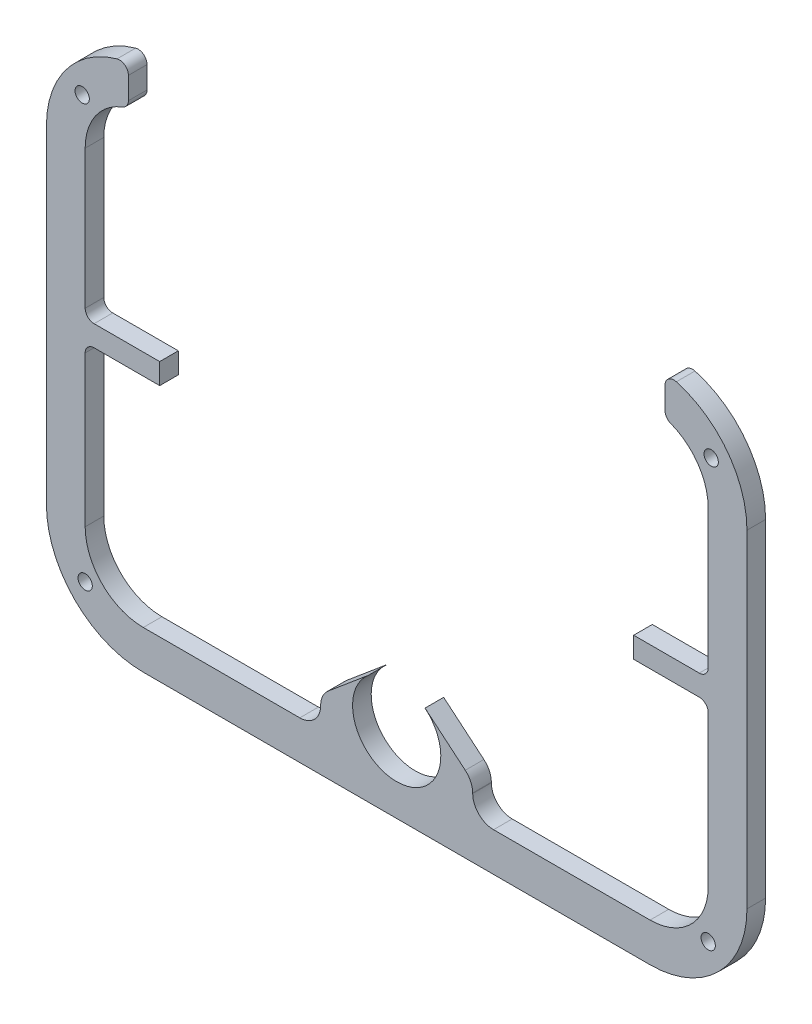
SolidWorks part; units mm, degrees
material "Delrin 2700 NC010, Low Viscosity Acetal Copolymer (SS)"
ref_plane "Front Plane" through (0, 0, 0) normal (0, 0, 1) x (1, 0, 0)
ref_plane "Top Plane" through (0, 0, 0) normal (0, 1, 0) x (1, 0, 0)
ref_plane "Right Plane" through (0, 0, 0) normal (1, 0, 0) x (0, 0, -1)
sketch "Sketch1" plane through (0, 0, 0) normal (0, 0, 1) x (1, 0, 0)
  line L0 (-21.59, -18.923) -> (-9.6321, -18.923)
  line L1 (21.59, 22.225) -> (-21.59, 22.225)
  line L2 (29.845, 13.97) -> (29.845, -13.97)
  line L3 (21.59, -22.225) -> (-21.59, -22.225)
  line L4 (-29.845, 13.97) -> (-29.845, -13.97)
  line L5 (29.845, 22.225) -> (-29.845, -22.225) construction
  line L6 (29.845, -22.225) -> (-29.845, 22.225) construction
  line L7 (9.6321, -18.923) -> (21.59, -18.923)
  line L8 (-26.543, -0.381) -> (-20.193, -0.381)
  line L9 (26.543, 1.397) -> (20.193, 1.397)
  line L10 (-26.543, 13.97) -> (-26.543, -13.97)
  line L11 (-1000, 0) -> (49000, 0) construction
  line L12 (-26.543, 0) -> (-26.543, -1.27)
  line L13 (26.543, 13.97) -> (26.543, -13.97)
  line L14 (21.59, 18.923) -> (-21.59, 18.923)
  line L15 (26.543, 1.397) -> (26.543, -0.381)
  line L16 (26.543, -0.381) -> (20.193, -0.381)
  line L17 (20.193, 1.397) -> (20.193, -0.381)
  line L18 (0, 18.923) -> (0, -18.415) construction
  line L19 (-20.193, 1.397) -> (-20.193, -0.381)
  line L20 (-26.543, 1.397) -> (-20.193, 1.397)
  line L21 (2.4164, -12.8683) -> (9.6321, -18.923)
  line L22 (-2.4164, -12.8683) -> (-9.6321, -18.923)
  line L36 (21.59, -18.923) -> (-21.59, -18.923) construction
  arc A0 (-2.4164, -12.8683) -> (2.4164, -12.8683) centre (0, -15.748) ccw
  arc A1 (-21.59, 22.225) -> (-29.845, 13.97) centre (-21.59, 13.97) ccw
  arc A2 (21.59, 22.225) -> (29.845, 13.97) centre (21.59, 13.97) cw
  arc A3 (29.845, -13.97) -> (21.59, -22.225) centre (21.59, -13.97) cw
  arc A4 (-21.59, -22.225) -> (-29.845, -13.97) centre (-21.59, -13.97) cw
  arc A7 (21.59, 18.923) -> (26.543, 13.97) centre (21.59, 13.97) cw
  arc A8 (-21.59, 18.923) -> (-26.543, 13.97) centre (-21.59, 13.97) ccw
  arc A13 (-21.59, -18.923) -> (-26.543, -13.97) centre (-21.59, -13.97) cw construction
  arc A14 (26.543, -13.97) -> (21.59, -18.923) centre (21.59, -13.97) cw construction
  arc A15 (-26.543, -13.97) -> (-21.59, -18.923) centre (-21.59, -13.97) ccw
  arc A16 (21.59, -18.923) -> (26.543, -13.97) centre (21.59, -13.97) ccw
  point P0 (0, 0)
  dimension "D4" = 7.5184
  dimension "D6" = 8.255
  dimension "D7" = 8.255
  dimension "D8" = 8.255
  dimension "D9" = 8.255
  dimension "D1" = 59.69
  dimension "D2" = 44.45
  dimension "D10" = 3.302
  dimension "D3" = 3.175
  dimension "D13" = 15.748
  dimension "D14" = 1.778
  dimension "D15" = 21.844
  dimension "D16" = 6.35
extrude "Boss-Extrude1" add sketch "Sketch1" along normal blind 1.5875 contours A4 L3 A3 L2 A2 L1 A1 L4 A16 L7 L21 A0 L22 L0 A15 L10 A8 L14 A7 L13 | L9 L17 L16 L13 | L20 L10 L8 L19 region at (-23.368, 0.508, 0) region at (23.368, 0.508, 0) region at (26.9009, 19.2809, 0)
sketch "Sketch2" plane through (0, 0, 1.5875) normal (0, 0, 1) x (1, 0, 0)
  line L1 (-9.6321, -18.923) -> (-6.477, -18.923)
  line L2 (-9.6321, -18.923) -> (-9.6321, -16.2756)
  line L3 (-9.6321, -16.2756) -> (-6.477, -16.2756)
  line L4 (-6.477, -18.923) -> (-6.477, -16.2756)
  line L5 (0, -1000) -> (0, 49000) construction
  line L6 (9.6321, -18.923) -> (9.6321, -16.2756)
  line L7 (9.6321, -16.2756) -> (6.477, -16.2756)
  line L8 (6.477, -18.923) -> (6.477, -16.2756)
  line L9 (9.6321, -18.923) -> (6.477, -18.923)
  line L10 (-29.845, 13.97) -> (-29.845, -13.97) construction
  line L11 (-21.59, 18.923) -> (21.59, 18.923)
  line L12 (-22.86, 18.7574) -> (-22.86, 22.225)
  line L13 (-22.86, 22.225) -> (22.86, 22.225)
  line L14 (22.86, 18.7574) -> (22.86, 22.225)
  line L16 (21.59, 18.923) -> (-21.59, 18.923) construction
  line L17 (-2.4164, -12.8683) -> (-9.6321, -18.923) construction
  line L18 (21.59, 22.225) -> (-21.59, 22.225) construction
  arc A0 (26.543, 13.97) -> (21.59, 18.923) centre (21.59, 13.97) ccw construction
  arc A1 (-21.59, 18.923) -> (-26.543, 13.97) centre (-21.59, 13.97) ccw construction
  arc A2 (22.86, 18.7574) -> (21.59, 18.923) centre (21.59, 13.97) ccw
  arc A3 (-21.59, 18.923) -> (-22.86, 18.7574) centre (-21.59, 13.97) ccw
  point P25 (0, 22.225)
  dimension "D1" = 6.477
  dimension "D2" = 6.985
extrude "Cut-Extrude1" cut sketch "Sketch2" against normal up to next
fillet "Fillet1" radius 1.778 4 edges at (6.477, -18.923, 0.7937) (6.477, -16.2756, 0.7937) (-6.477, -18.923, 0.7937) (-6.477, -16.2756, 0.7937)
fillet "Fillet2" radius 0.762 4 edges at (22.86, 22.1267, 0.7937) (22.86, 18.7574, 0.7937) (-22.86, 18.7574, 0.7937) (-22.86, 22.1267, 0.7937)
fillet "Fillet3" radius 0.762 4 edges at (-26.543, -0.381, 0.7937) (26.543, -0.381, 0.7937) (26.543, 1.397, 0.7937) (-26.543, 1.397, 0.7937)
sketch "Sketch3" plane through (0, 0, 1.5875) normal (0, 0, 1) x (1, 0, 0)
  circle A0 centre (-25.019, -16.51) radius 0.6096 construction
  circle A1 centre (-25.019, 16.256) radius 0.6096 construction
  circle A2 centre (25.019, 16.256) radius 0.6096 construction
  circle A3 centre (25.019, -16.51) radius 0.6096 construction
  circle A4 centre (-25.019, -16.51) radius 0.6096 construction
  circle A5 centre (-25.019, 16.256) radius 0.6096 construction
  circle A6 centre (25.019, 16.256) radius 0.6096 construction
  circle A7 centre (25.019, -16.51) radius 0.6096 construction
  circle A8 centre (-26.797, 17.78) radius 0.6096
  circle A9 centre (-26.543, -18.034) radius 0.6096
  circle A10 centre (26.797, 17.78) radius 0.6096
  circle A11 centre (26.543, -18.034) radius 0.6096
  dimension "D1" = 1.524
  dimension "D2" = 1.778
  dimension "D3" = 1.524
  dimension "D4" = 1.524
  dimension "D5" = 1.778
  dimension "D6" = 1.524
extrude "Cut-Extrude2" cut sketch "Sketch3" against normal up to surface (1.5875 mm away) up to face at (0, -2.0741, 0)
